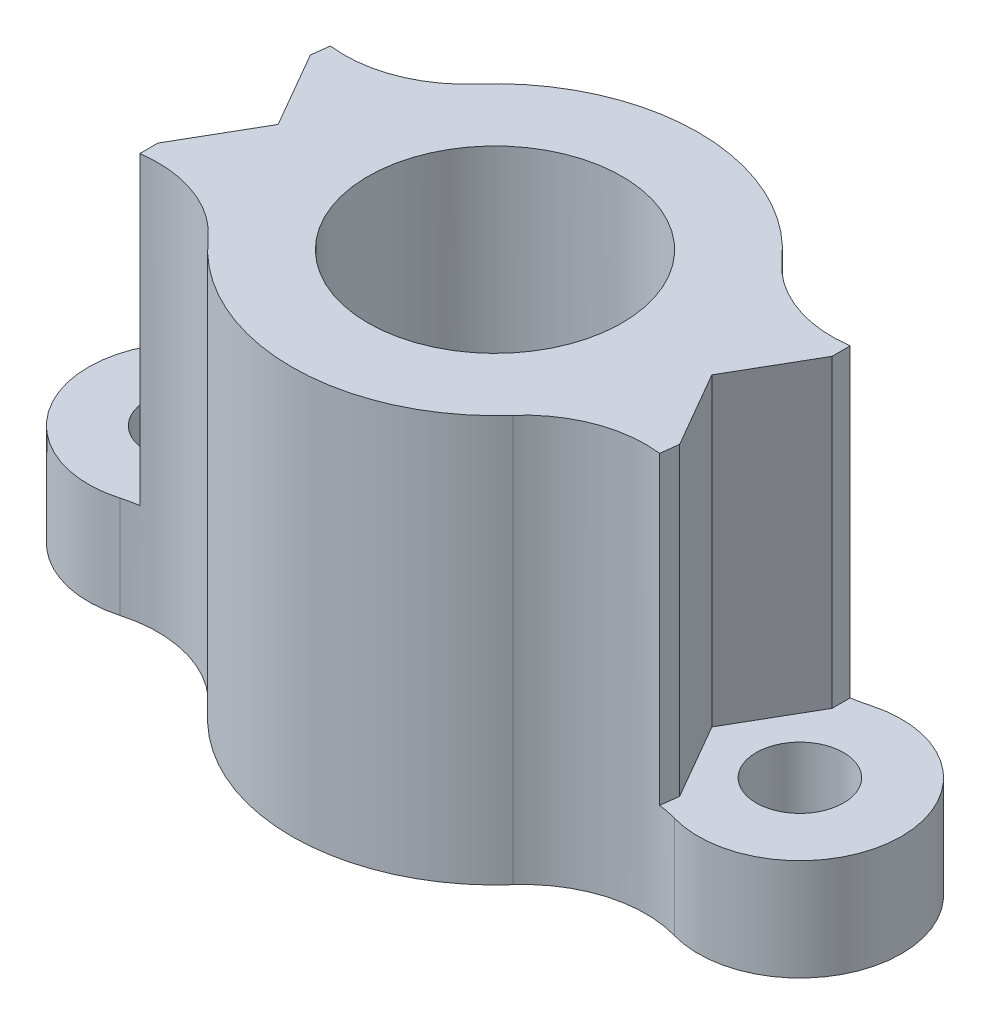
SolidWorks part; units mm, degrees
material "ABS"
ref_plane "Front Plane" through (0, 0, 0) normal (0, 0, 1) x (1, 0, 0)
ref_plane "Top Plane" through (0, 0, 0) normal (0, 1, 0) x (1, 0, 0)
ref_plane "Right Plane" through (0, 0, 0) normal (1, 0, 0) x (0, 0, -1)
sketch "Sketch1" plane through (0, 0, 0) normal (0, 1, 0) x (1, 0, 0)
  line L0 (0, 0) -> (0, -5.2917) construction
  line L1 (0, 0) -> (2.6508, 0) construction
  arc A0 (-7.5, -6.6144) -> (7.5, -6.6144) centre (0, 0) ccw
  arc A1 (13.6364, -4.8105) -> (13.6364, 4.8105) centre (15, 0) ccw
  arc A2 (-13.6364, 4.8105) -> (-13.6364, -4.8105) centre (-15, 0) ccw
  arc A3 (-13.6364, 4.8105) -> (-7.5, 6.6144) centre (-12, 10.583) ccw
  arc A4 (-13.6364, -4.8105) -> (-7.5, -6.6144) centre (-12, -10.583) cw
  arc A5 (13.6364, -4.8105) -> (7.5, -6.6144) centre (12, -10.583) ccw
  arc A6 (13.6364, 4.8105) -> (7.5, 6.6144) centre (12, 10.583) cw
  arc A7 (7.5, 6.6144) -> (-7.5, 6.6144) centre (0, 0) ccw
  dimension "D1" = 20
  dimension "D2" = 10
  dimension "D3" = 12
extrude "Boss-Extrude1" add sketch "Sketch1" along normal blind 20
sketch "Sketch2" plane through (0, 20, 0) normal (0, 1, 0) x (1, 0, 0)
  line L0 (-12.8349, 3.75) -> (-12.7277, 4.6273)
  line L1 (10.6699, 0) -> (12.8349, -3.75)
  line L6 (12.8349, 3.75) -> (10.6699, 0)
  line L9 (-12.8349, -3.75) -> (-10.6699, 0)
  line L10 (-10.6699, 0) -> (-12.8349, 3.75)
  line L13 (-12.8349, -3.75) -> (-12.8349, -4.6414)
  line L14 (12.8349, -3.75) -> (12.7277, -4.6273)
  line L15 (12.8349, 3.75) -> (12.8349, 4.6414)
  line L16 (-17.1651, -3.75) -> (-15, -3.75) [skipped]
  line L17 (-18.2476, -1.875) -> (-17.1651, -3.75) [skipped]
  line L18 (-12.8349, 3.75) -> (-15, 3.75) [skipped]
  line L19 (-17.1651, 3.75) -> (-18.2476, 1.875) [skipped]
  line L20 (17.1651, 3.75) -> (15, 3.75) [skipped]
  line L21 (19.3301, 0) -> (18.2476, 1.875) [skipped]
  line L22 (17.1651, -3.75) -> (18.2476, -1.875) [skipped]
  line L23 (12.8349, -3.75) -> (15, -3.75) [skipped]
  circle A0 centre (0, 0) radius 6.25
  circle A1 centre (15, 0) radius 2.15
  circle A2 centre (-15, 0) radius 2.15
  arc A3 (-13.6364, 4.8105) -> (-13.6364, -4.8105) centre (-15, 0) ccw construction
  arc A4 (13.6364, -4.8105) -> (13.6364, 4.8105) centre (15, 0) ccw construction
  circle A7 centre (15, 0) radius 3.75 construction
  circle A8 centre (-15, 0) radius 3.75 construction
  arc A17 (-7.5, -6.6144) -> (-13.6364, -4.8105) centre (-12, -10.583) ccw
  arc A18 (-7.5, -6.6144) -> (7.5, -6.6144) centre (0, 0) ccw
  arc A19 (13.6364, -4.8105) -> (7.5, -6.6144) centre (12, -10.583) ccw
  arc A20 (13.6364, -4.8105) -> (13.6364, 4.8105) centre (15, 0) ccw
  arc A21 (7.5, 6.6144) -> (13.6364, 4.8105) centre (12, 10.583) ccw
  arc A22 (7.5, 6.6144) -> (-7.5, 6.6144) centre (0, 0) ccw
  arc A23 (-13.6364, 4.8105) -> (-7.5, 6.6144) centre (-12, 10.583) ccw
  arc A24 (-13.6364, 4.8105) -> (-13.6364, -4.8105) centre (-15, 0) ccw
  arc A25 (-12.8349, -4.6414) -> (-13.6364, -4.8105) centre (-12, -10.583) ccw
  arc A27 (13.6364, -4.8105) -> (12.7277, -4.6273) centre (12, -10.583) ccw
  arc A28 (13.6364, -4.8105) -> (13.6364, 4.8105) centre (15, 0) ccw
  arc A29 (12.8349, 4.6414) -> (13.6364, 4.8105) centre (12, 10.583) ccw
  arc A31 (-13.6364, 4.8105) -> (-12.7277, 4.6273) centre (-12, 10.583) ccw
  arc A32 (-13.6364, 4.8105) -> (-13.6364, -4.8105) centre (-15, 0) ccw
  dimension "D1" = 12.5
  dimension "D2" = 4.3
  dimension "D3" = 4.3301
  dimension "D5" = 4.3301
  dimension "D6" = 7.5
  dimension "D4" = 0
extrude "Cut-Extrude1" cut sketch "Sketch2" against normal offset from surface (11 mm away) 9 contours A0 region at (0, 20, 0) up to face at (0, 0, 0)
extrude "Cut-Extrude2" cut sketch "Sketch2<3>" against normal through all contours A2 | A1 region at (15, 20, 0) region at (-15, 20, 0)
sketch "Sketch2<3>" plane through (0, 20, 0) normal (0, 1, 0) x (1, 0, 0) same geometry as "Sketch2"
extrude "Cut-Extrude3" cut sketch "Sketch2<4>" against normal offset from surface (15 mm away) 5 contours A2 | A1 region at (-11.8708, 20, -1.8066) region at (13.2668, 20, -4.5784) up to face at (-15, 0, 2.15)
sketch "Sketch2<4>" plane through (0, 20, 0) normal (0, 1, 0) x (1, 0, 0) same geometry as "Sketch2"
sketch "Sketch3" plane through (0, 9, 0) normal (0, 1, 0) x (1, 0, 0)
  circle A0 centre (0, 0) radius 2.25
  dimension "D1" = 4.5
extrude "Cut-Extrude4" cut sketch "Sketch3" against normal through all
sketch "Sketch4" plane through (0, 0, 0) normal (0, -1, 0) x (1, 0, 0)
  circle A0 centre (0, 0) radius 4
  dimension "D1" = 8
extrude "Cut-Extrude5" cut sketch "Sketch4" against normal offset from surface (4 mm away) 5 up to face at (0, 9, 2.25)
